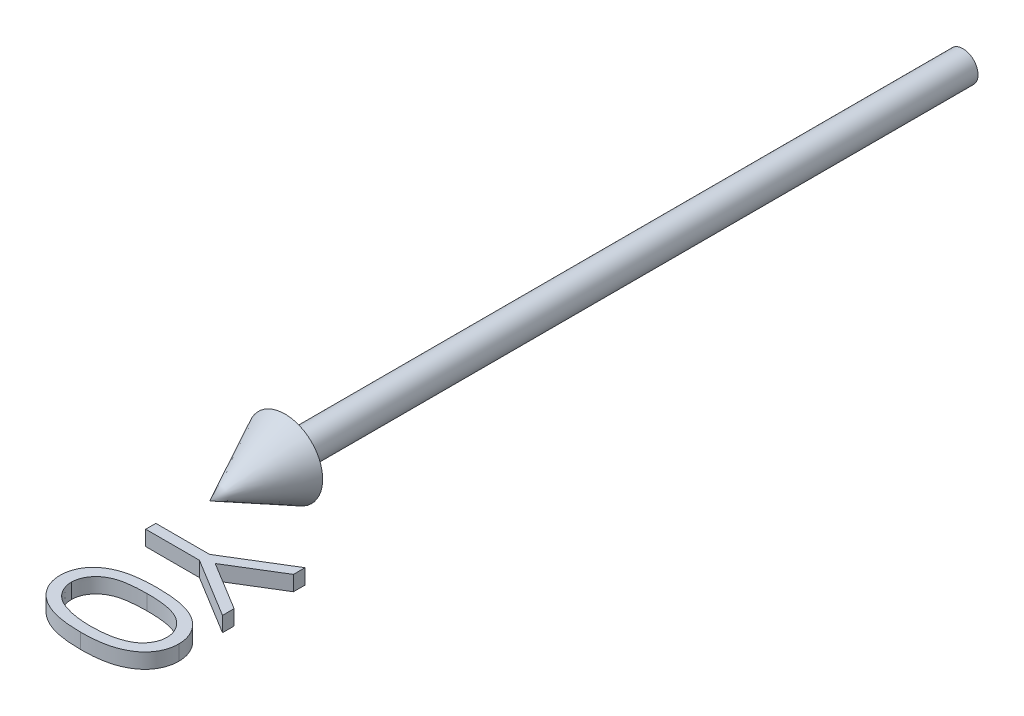
SolidWorks part; units mm, degrees
ref_plane "Front Plane" through (0, 0, 0) normal (0, 0, 1) x (1, 0, 0)
ref_plane "Top Plane" through (0, 0, 0) normal (0, 1, 0) x (1, 0, 0)
ref_plane "Right Plane" through (0, 0, 0) normal (1, 0, 0) x (0, 0, -1)
sketch "Sketch2" plane through (0, 0, 0) normal (0, 1, 0) x (1, 0, 0)
  line L0 (0, 41.95) -> (0, -114.4521) construction
  line L1 (-36.8894, 0) -> (41.4965, 0) construction
  line L2 (0, -100) -> (5, -90)
  line L3 (5, -90) -> (2, -90)
  line L4 (2, -90) -> (2, 0)
  line L5 (2, 0) -> (0, 0)
  line L6 (0, 0) -> (0, -100)
  dimension "D1" = 100
  dimension "D2" = 2
  dimension "D3" = 10
  dimension "D4" = 5
revolve "Revolve1" add sketch "Sketch2" angle 360 about L0
sketch "Sketch3" plane through (0, 0, 0) normal (0, 1, 0) x (1, 0, 0)
  line L0 (0, -101.5706) -> (0, -127.8138) construction
  text T0 "Y0\r\n" font "Century Gothic" height 15
extrude "Boss-Extrude1" add sketch "Sketch3" against normal blind 1 and the other way blind 1 separate body
equation "\"frame_arrow_length\"=100"
equation "\"D1@Sketch2\"=\"frame_arrow_length\""
equation "\"frame_arrow_odA\"=4"
equation "\"D2@Sketch2\"=\"frame_arrow_odA\"/2"
equation "\"frame_arrow_head_od\"=5"
equation "\"D4@Sketch2\"=\"frame_arrow_head_od\""
equation "\"frame_arrow_head_length\"=10"
equation "\"D3@Sketch2\"=\"frame_arrow_head_length\""
equation "\"tvarobot_theta1\"=30"
equation "\"link0_ringA_odA\"= 40"
equation "\"link0_ringA_odB\"= 25"
equation "\"link0_ringA_id\"= 20"
equation "\"link0_ringA_thickness\"= (\"link0_ringA_odB\" - \"link0_ringA_id\")/2"
equation "\"link0_ringA_height\"= 3"
equation "\"link0_ringA_heightA\"= 1.5"
equation "\"link0_ringA_heightB\"=\"link0_ringA_height\"-\"link0_ringA_heightA\""
equation "\"link0_ringB_odA\"= 40"
equation "\"link0_ringB_odB\"= 29"
equation "\"link0_ringB_id\"= \"link0_shaftA_bearing_id\"+1"
equation "\"link0_ringB_thickness\"= (\"link0_ringB_odB\" - \"link0_ringB_id\")/2"
equation "\"link0_ringB_height\"= 3"
equation "\"link0_ringB_heightA\"= 1.5"
equation "\"link0_ringB_heightB\"=\"link0_ringB_height\"-\"link0_ringB_heightA\""
equation "\"link0_shaftA_bearing_od\"=27"
equation "\"link0_shaftA_bearing_id\"=20"
equation "\"link0_shaftA_thrust_bearing_od\"=35"
equation "\"link0_shaftA_thrust_bearing_id\"=20.04"
equation "\"link0_shaftA_retaining_ring_id\"=18.5"
equation "\"link0_shaftA_retaining_ring_groove_width\"=1.5"
equation "\"link0_shaftA_spline_length\"=8.0"
equation "\"link0_shaftA_spline_depth\"=1.0"
equation "\"link0_shaftA_spline_width\"=4.0"
equation "\"link0_shaftA_odA\"=\"link0_shaftA_bearing_id\""
equation "\"link0_shaftA_odB\"=35"
equation "\"link0_shaftA_odC\"=\"link0_shaftA_bearing_id\""
equation "\"link0_shaftA_odD\"=\"link0_shaftA_odC\"-2*\"link0_shaftA_spline_depth\""
equation "\"link0_shaftA_odE\"=\"link0_shaftA_bearing_id\""
equation "\"link0_shaftA_odF\"=\"link0_shaftA_odE\"-2*\"link0_shaftA_spline_depth\""
equation "\"link0_shaftA_idA\"=10"
equation "\"link0_shaftA_idB\"=6"
equation "\"link0_shaftA_length\"=39.5"
equation "\"link0_shaftA_lengthA\"=8.0"
equation "\"link0_shaftA_lengthB\"=12.0"
equation "\"link0_shaftA_lengthC\"=35.0"
equation "\"link0_shaftA_lengthD\"=39.0"
equation "\"link0_shaftA_lengthE\"=\"link0_shaftA_length\"-\"link0_shaftA_lengthD\""
equation "\"link0_shaftA_offsetX\"=11"
equation "\"link0_shaftA_offsetY\"=0"
equation "\"link0_shaftA_bolt_pattern_dia\"=14"
equation "\"link0_motor_center_dist\"=26"
equation "\"link0_46t_pulley_spline_length\"=8"
equation "\"link0_46t_pulley_spline_depth\"=\"link0_shaftA_spline_depth\"*1.025"
equation "\"link0_46t_pulley_spline_width\"=\"link0_shaftA_spline_width\"*1.05"
equation "\"link0_46t_pulley_idA\"=\"link0_shaftA_bearing_id\"*1.025"
equation "\"link0_46t_pulley_idB\"=\"link0_46t_pulley_idA\"-2*\"link0_46t_pulley_spline_depth\""
equation "\"link0_shaftB_spline_length\"=10"
equation "\"link0_shaftB_spline_depth\"=1.0"
equation "\"link0_shaftB_spline_width\"=1.25"
equation "\"link0_shaftB_length\"=7"
equation "\"link0_shaftB_lengthA\"=1.5"
equation "\"link0_shaftB_lengthB\"=2.75"
equation "\"link0_shaftB_odA\"=32"
equation "\"link0_shaftB_odB\"=22"
equation "\"link0_shaftB_odC\"=20"
equation "\"link0_shaftB_idA\"=10"
equation "\"link0_shaftB_bolt_diameter\"=19"
equation "\"link0_shaftB_bearing_od\"=27"
equation "\"link0_shaftB_bearing_id\"=20"
equation "\"link0_motor_length\"=46.5"
equation "\"link0_motor_width\"=28.5"
equation "\"link0_motor_height\"=34"
equation "\"link0_motor_offset\"=8"
equation "\"link0_shellA_thickness\"=2.5"
equation "\"link0_shellB_thickness\"=\"link0_shellA_thickness\""
equation "\"link0_plateA_shellA_height\"=48"
equation "\"link0_shellA_width\" =\"link0_plateA_width\""
equation "\"link0_shellA_height\" = \"link0_plateA_shellA_height\"-\"link0_plateA_height\""
equation "\"link0_shellA_length\" = \"link0_plateA_lengthB\" "
equation "\"link0_shellB_length\"=\"link0_shellA_length\""
equation "\"link0_shellA_radius\" = 0.375*25.4"
equation "\"link0_shellA_radiusA\"= \"link0_plateA_radiusA\""
equation "\"link0_shellA_radiusB\"= \"link0_plateA_radiusB\""
equation "\"link0_shellA_radiusC\"= 3"
equation "\"link0_postA_height\"=7"
equation "\"link0_postA_width\"=16"
equation "\"link0_postA_length\"=20"
equation "\"link0_postA_posX\"=22"
equation "\"link0_postA_posY\"=17.5"
equation "\"link0_postA_pocket_width\"=6.0"
equation "\"link0_postA_pocket_length\"=2.5"
equation "\"link0_postA_pocket_depth\"=9"
equation "\"link0_postA_pocket_posZ\"=10"
equation "\"link0_postB_height\"=7"
equation "\"link0_postB_width\"=16"
equation "\"link0_postB_length\"=20"
equation "\"link0_postB_posX\"=22"
equation "\"link0_postB_posY\"=17.5"
equation "\"link0_postB_id\"=3.0"
equation "\"link0_postB_pocket_width\"=6.0"
equation "\"link0_postB_pocket_length\"=2.5"
equation "\"link0_postB_pocket_depth\"=9"
equation "\"link0_postB_pocket_posZ\"=10"
equation "\"link0_postC_height\"=7"
equation "\"link0_postC_width\"=16"
equation "\"link0_postC_length\"=20"
equation "\"link0_postC_posX\"=22"
equation "\"link0_postC_posY\"=17.5"
equation "\"link0_postC_id\"=3.0"
equation "\"link0_postC_pocket_width\"=6.0"
equation "\"link0_postC_pocket_length\"=2.5"
equation "\"link0_postC_pocket_depth\"=9"
equation "\"link0_postC_pocket_posZ\"=10"
equation "\"link0_postD_height\"=7"
equation "\"link0_postD_width\"=16"
equation "\"link0_postD_length\"=20"
equation "\"link0_postD_posX\"=22"
equation "\"link0_postD_posY\"=17.5"
equation "\"link0_postD_id\"=3.0"
equation "\"link0_postD_pocket_width\"=6.0"
equation "\"link0_postD_pocket_length\"=3.0"
equation "\"link0_postD_pocket_depth\"=9"
equation "\"link0_postD_pocket_posZ\"=10"
equation "\"link0_postE_height\"=5"
equation "\"link0_postE_width\"=16"
equation "\"link0_postE_length\"=\"link0_plateE_lengthA\"-\"link0_lip_height\""
equation "\"link0_postE_posZ\"=22"
equation "\"link0_postE_posX\"=17.5"
equation "\"link0_postE_posY\"=22"
equation "\"link0_postE_id\"=3.0"
equation "\"link0_postE_cbore_id\"=6.5"
equation "\"link0_postE_hole_id\"=3"
equation "\"link0_postF_posZ\"=22"
equation "\"link0_postF_posX\"=17.5"
equation "\"link0_postF_posY\"=\"link0_plateB_lengthA\"+4"
equation "\"link0_postF_id\"=3.0"
equation "\"link0_postF_cbore_id\"=6.5"
equation "\"link0_postF_hole_id\"=3"
equation "\"link0_postG_posZ\"=22"
equation "\"link0_postG_posX\"=17.5"
equation "\"link0_postG_posY\"=\"link0_plateB_lengthA\"+12"
equation "\"link0_postG_id\"=3.0"
equation "\"link0_postG_cbore_id\"=6.5"
equation "\"link0_postG_hole_id\"=3"
equation "\"link0_postHIJ_posY\"=6"
equation "\"link0_postH_posX\"=28"
equation "\"link0_postH_posY\"=20"
equation "\"link0_postH_posZ\"=20"
equation "\"link0_postH_length\"=10"
equation "\"link0_postI_posX\"=28"
equation "\"link0_postI_posY\"=20"
equation "\"link0_postI_posZ\"=135"
equation "\"link0_postI_length\"=10"
equation "\"link0_postJ_posX\"=28"
equation "\"link0_postJ_posY\"=20"
equation "\"link0_postJ_posZ\"=175"
equation "\"link0_postJ_length\"=10"
equation "\"link0_postK_posX\"=28"
equation "\"link0_postK_posY\"=20"
equation "\"link0_postK_posZ\"=175"
equation "\"link0_postK_length\"=10"
equation "\"link0_postL_posX\"=28"
equation "\"link0_postL_posY\"=20"
equation "\"link0_postL_posZ\"=135"
equation "\"link0_postL_length\"=10"
equation "\"link0_postM_posX\"=28"
equation "\"link0_postM_posY\"=20"
equation "\"link0_postM_posZ\"=35"
equation "\"link0_postM_length\"=10"
equation "\"link0_plateA_lengthA\"=30"
equation "\"link0_plateA_lengthB\"=150"
equation "\"link0_plateA_lengthC\"=30"
equation "\"link0_plateA_length\"=\"link0_plateA_lengthA\"+\"link0_plateA_lengthB\"+\"link0_plateA_lengthC\""
equation "\"link0_plateA_width\"=  68"
equation "\"link0_plateA_height\"= \"link0_plateA_radiusA\""
equation "\"link0_plateA_thickness\"=\"link0_shellA_thickness\""
equation "\"link0_plateA_radius\"= 9.5"
equation "\"link0_plateA_radiusA\"= 18"
equation "\"link0_plateA_radiusB\"= 18"
equation "\"link0_plateA_radiusC\"= 3"
equation "\"link0_plateB_length\"= 40"
equation "\"link0_plateB_width\"= \"link0_plateA_width\"*1.005"
equation "\"link0_plateB_height\"= \"link0_plateA_shellA_height\"*1.005"
equation "\"link0_plateB_lengthA\"=\"link0_lip_height\"+\"link0_plateD_thickness\"+\"link0_motor_mount_thickness\""
equation "\"link0_plateB_lengthB\"=\"link0_plateB_height\"-\"link0_plateB_lengthA\""
equation "\"link0_plateB_radiusA\"= \"link0_plateA_radiusA\""
equation "\"link0_plateB_radiusB\"= \"link0_plateA_radiusB\""
equation "\"link0_plateB_radiusC\"= 3"
equation "\"link0_plateB_idA\"=\"link0_shaftA_odC\"+1"
equation "\"link0_plateB_idB\"=\"link0_shaftA_bearing_od\"-2"
equation "\"link0_plateB_idC\"=\"link0_shaftA_bearing_od\"*1.005"
equation "\"link0_plateB_idD\"=\"link0_shaftA_thrust_bearing_od\"+1 "
equation "\"link0_plateB_depthA\"=1.0"
equation "\"link0_plateB_depthB\"=2.0"
equation "\"link0_plateB_depthC\"=8"
equation "\"link0_plateB_depthD\"=\"link0_plateB_length\"-\"link0_lip_height\"-\"link0_plateD_thickness\" "
equation "\"link0_plateC_length\"=\"link0_plateB_length\""
equation "\"link0_plateC_width\"= \"link0_plateB_width\""
equation "\"link0_plateC_height\"= .1*25.4"
equation "\"link0_plateA_hole_od\" = 0.1*25.4"
equation "\"link0_plateA_hole_delx\" = 0.5*25.4"
equation "\"link0_plateA_hole_delz\" = 0.75*25.4"
equation "\"link0_plateA_hole_offx\" = 0.0*25.4"
equation "\"link0_plateA_hole_offz\" = \"link0_plateA_length\"/2"
equation "\"link0_plateB_hole_od\" = 0.1*25.4"
equation "\"link0_plateB_hole_delx\"= 0.75*25.4"
equation "\"link0_plateB_hole_delz\"= 0.75*25.4"
equation "\"link0_plateB_hole_offx\"= 0.0*25.4"
equation "\"link0_plateB_hole_offz\"= 0.0*25.4"
equation "\"link0_plateC_hole_od\"= 0.1*25.4"
equation "\"link0_plateC_hole_delx\"= 0.75*25.4"
equation "\"link0_plateC_hole_delz\"= 0.75*25.4"
equation "\"link0_plateC_hole_offx\"= 0.0*25.4"
equation "\"link0_plateC_hole_offz\"= 0.0*25.4"
equation "\"link0_plateD_height\"=\"link0_plateB_height\"-2*\"link0_shellA_thickness\""
equation "\"link0_plateD_width\"=\"link0_plateB_width\"-2*\"link0_shellA_thickness\""
equation "\"link0_plateD_thickness\"=10"
equation "\"link0_plateD_radiusA\"=\"link0_plateB_radiusA\"-\"link0_shellA_thickness\""
equation "\"link0_plateD_odA\"= .375*25.4"
equation "\"link0_plateD_odB\"= .375*25.4"
equation "\"link0_plateD_bearing_id\"=20"
equation "\"link0_plateD_bearing_od\"=27"
equation "\"link0_plateE_radiusA\"=\"link0_plateA_radiusA\""
equation "\"link0_plateE_radiusB\"=\"link0_plateA_radiusB\""
equation "\"link0_plateE_radiusC\"=8.0"
equation "\"link0_plateE_length\"=30"
equation "\"link0_plateE_lengthA\"=16"
equation "\"link0_plateE_height\"=\"link0_plateB_height\""
equation "\"link0_plateE_width\"=\"link0_plateB_width\""
equation "\"link0_plateE_odA\"=\"gantry_coupler_id\"*0.99"
equation "\"link0_plateE_idA\"=\"link0_plateE_odA\"-20.0"
equation "\"link0_plateE_spline_depth\"=\"link0_poleA_spline_depth\"*1.05"
equation "\"link0_plateE_spline_width\"=\"link0_poleA_spline_width\"*1.075"
equation "\"link0_plateE_spline_length\"=\"link0_poleA_spline_length\""
equation "\"link0_plateE_coupler_length\"=46"
equation "\"link0_lip_height\"=5.0"
equation "\"link0_lip_thickness\"=2.0"
equation "\"link0_motor_mount_thickness\"=8.0"
equation "\"link0_motor_mount_idA\"=22"
equation "\"link0_motor_mount_idB\"=\"link0_shaftB_bearing_od\"*1.005"
equation "\"link0_motor_mount_idC\"=\"link0_shaftB_bearing_od\"-2"
equation "\"link0_motor_mount_depthA\"=5.5"
equation "\"link0_motor_mount_height\"=\"link0_plateD_height\""
equation "\"link0_motor_mount_width\"=\"link0_plateD_width\""
equation "\"link0_motor_mountL_height\"=36"
equation "\"link0_motor_mountL_heightA\"=12"
equation "\"link0_motor_mountL_length\"=50"
equation "\"link0_motor_mountL_lengthA\"=36"
equation "\"gantry_coupler_od\"=25.4*2.0"
equation "\"gantry_coupler_id\"=1.645*25.4"
equation "\"gantry_coupler_offsetX\"=\"link0_plateE_width\"/2"
equation "\"link0_poleA_odA\"=20"
equation "\"link0_poleA_odB\"=36"
equation "\"link0_poleA_idA\"=\"link0_poleA_odA\"-2*\"link0_poleA_thickness\""
equation "\"link0_poleA_idB\"=(\"link0_plateE_idA\"/2+1.5*\"link0_lip_thickness\")*1.04"
equation "\"link0_poleA_thickness\"=3.5"
equation "\"link0_poleA_length\"=100"
equation "\"link0_poleA_lengthA\"=18.5"
equation "\"link0_poleA_lengthB\"=80"
equation "\"link0_poleA_gasket_thickness\"=1.5"
equation "\"link0_poleA_spline_depth\"=1.0"
equation "\"link0_poleA_spline_width\"=4.0"
equation "\"link0_poleA_spline_length\"=10.0"
equation "\"link1_plateB_length\"=30"
equation "\"link1_lip_height\"=\"link0_lip_height\""
equation "\"link0_tension_plateA_width\"=12"
equation "\"link0_tension_plateA_lengthA\"=10.5"
equation "\"link0_tension_plateB_width\"=\"link0_tension_plateA_width\""
equation "\"link0_tension_plateB_lengthA\"=\"link0_tension_plateA_lengthA\""
equation "\"link0_tension_wheelA_posZ\"=7"
equation "\"link0_tension_wheelA_posX\"=\"link0_plateD_height\"/2-\"link0_tension_plateA_lengthA\""
equation "\"link0_m2_clear_hole_id\"=2.35"
equation "\"link0_m2_insert_hole_id\"=2.5"
equation "\"link0_m2_tap_hole_id\"=1.75"
equation "\"link0_m2_nut_socket_width\"=4.25"
equation "\"link0_m2_nut_socket_depth\"=2.5"
equation "\"link0_m2_cbore_id\"=3.75"
equation "\"link0_m2_cbore_depth\"=7"
equation "\"link0_m2_5_clear_hole_id\"=2.75"
equation "\"link0_m2_5_insert_hole_id\"=2.75"
equation "\"link0_m2_5_tap_hole_id\"=2.25"
equation "\"link0_m2_5_nut_socket_width\"=5.25"
equation "\"link0_m2_5_nut_socket_depth\"=2.5"
equation "\"link0_m2_5_cbore_id\"=4.75"
equation "\"link0_m2_5_cbore_depth\"=2.5"
equation "\"link0_m2_5_insert_access_length\"=6.0"
equation "\"link0_m2_5_insert_access_width\"=3.0"
equation "\"link0_m3_clear_hole_id\"=3.25"
equation "\"link0_m3_insert_hole_id\"=3"
equation "\"link0_m3_tap_hole_id\"=2.75"
equation "\"link0_m3_nut_socket_width\"=5.75"
equation "\"link0_m3_nut_socket_depth\"=4.0"
equation "\"link0_m3_cbore_id\"=5.75"
equation "\"link0_m3_cbore_depth\"=3.5"
equation "\"link0_m3_insert_access_length\"=4.5"
equation "\"link0_m3_insert_access_width\"=3.5"
equation "\"link0_rpi_mount_height\"=6"
equation "\"link0_rpi_mount_width\"=49"
equation "\"link0_rpi_mount_length\"=58"
equation "\"link0_rpi_mount_post_od\"=6"
equation "\"link0_rpi_mount_posZ\"=72"
equation "\"link0_rpi_mount_posX\"=11.5"
equation "\"link0_mcu_mount_height\"=5"
equation "\"link0_mcu_mount_width\"=49"
equation "\"link0_mcu_mount_length\"=58"
equation "\"link0_mcu_mount_post_od\"=6"
equation "\"link0_mcu_mount_posZ\"=164"
equation "\"link0_mcu_mount_posX\"=4"
equation "\"link0_pwr_mount_height\"=4"
equation "\"link0_pwr_mount_width\"=15.75"
equation "\"link0_pwr_mount_length\"=75.75"
equation "\"link0_pwr_mount_post_od\"=6"
equation "\"link0_pwr_mount_posZ\"=75"
equation "\"link0_pwr_mount_posX\"=16"
equation "\"link0_pwr_board_height\"=6"
equation "\"link0_pwr_board_width\"=21"
equation "\"link0_pwr_board_length\"=80"
